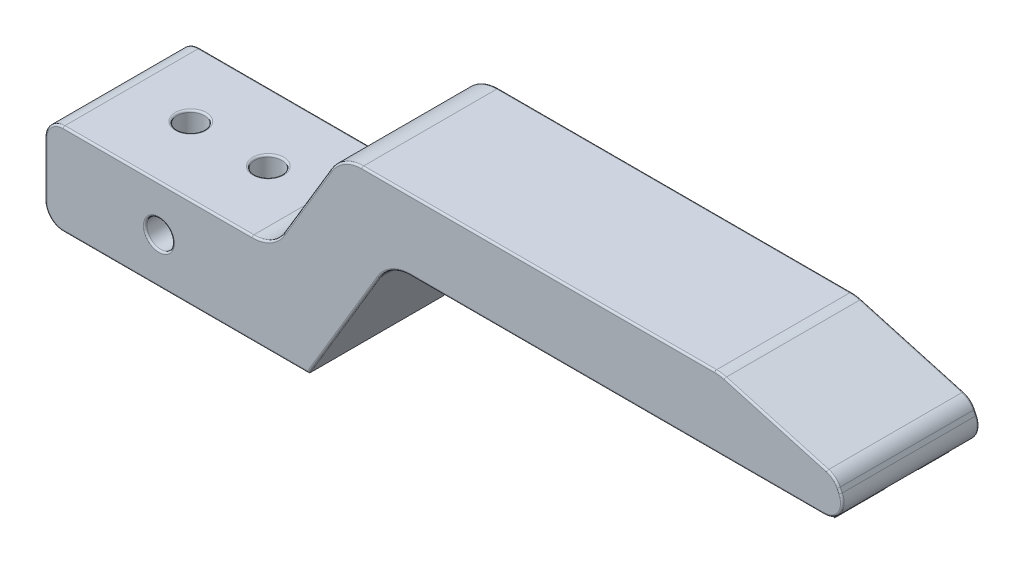
SolidWorks part; units mm, degrees
ref_plane "Plan de face" through (0, 0, 0) normal (0, 0, 1) x (1, 0, 0)
ref_plane "Plan de dessus" through (0, 0, 0) normal (0, 1, 0) x (1, 0, 0)
ref_plane "Plan de droite" through (0, 0, 0) normal (1, 0, 0) x (0, 0, -1)
sketch "Esquisse1" plane through (0, 0, 0) normal (0, 0, 1) x (1, 0, 0)
  line L0 (-20.9618, 39.858) -> (14.6887, 39.858)
  line L1 (14.6887, 39.858) -> (29.918, 39.858)
  line L2 (29.918, 39.858) -> (27.8943, 43.9947)
  line L3 (27.8943, 43.9947) -> (15.2797, 47.558)
  line L4 (15.2797, 47.558) -> (-26.2627, 47.558)
  line L5 (-20.9618, 39.858) -> (-29.8438, 24.9927)
  line L6 (-29.8438, 24.9927) -> (-58.7705, 24.9927)
  line L7 (-58.7705, 24.9927) -> (-58.7705, 34.9927)
  line L8 (-58.7705, 34.9927) -> (-33.7705, 34.9927)
  line L9 (-33.7705, 34.9927) -> (-26.2627, 47.558)
  line L10 (-20.9618, 39.858) -> (-20.9618, 34.2142) construction
  line L11 (-20.9618, 39.858) -> (-62.876, 39.858) construction
  circle A2 centre (-46.2705, 29.9927) radius 1.5
  point P0 (27.8943, 43.9947)
  dimension "D1" = 10
  dimension "D3" = 25
  dimension "D6" = 3
  dimension "D2" = 8.5
  dimension "D4" = 12.5
  dimension "D5" = 5
  dimension "D7" = 7.7
extrude "Boss.-Extru.1" add sketch "Esquisse1" along normal blind 15
fillet "Congé1" radius 2 2 edges at (29.918, 39.858, 7.5) (27.8943, 43.9947, 7.5)
fillet "Congé3" radius 4 1 edges at (-20.9618, 39.858, 7.5)
fillet "Congé5" radius 4 3 edges at (-33.7705, 34.9927, 7.5) (15.2797, 47.558, 7.5) (-26.2627, 47.558, 7.5)
fillet "Congé6" radius 2 2 edges at (-58.7705, 24.9927, 7.5) (-58.7705, 34.9927, 7.5)
sketch "Esquisse2" plane through (0, 24.9927, 0) normal (0, -1, 0) x (1, 0, 0)
  line L1 (-56.7705, 0) -> (-56.7705, 15) construction
  line L2 (-36.0401, 15) -> (-56.7705, 15) construction
  circle A0 centre (-50.2705, 7.5) radius 1.5
  circle A1 centre (-41.7705, 7.5) radius 1.5
  dimension "D2" = 3
  dimension "D4" = 3
  dimension "D1" = 6.5
  dimension "D3" = 7.5
  dimension "D5" = 8.5
extrude "Enlèv. mat.-Extru.2" cut sketch "Esquisse2" against normal through all contours A0 | A1
fillet "Congé8" radius 0.2 4 edges at (-48.7705, 24.9927, 7.5) (-40.2705, 24.9927, 7.5) (-40.2705, 34.9927, 7.5) (-48.7705, 34.9927, 7.5)
sketch "Esquisse3" plane through (0, 39.858, 0) normal (0, -1, 0) x (1, 0, 0)
  line L0 (-17.5068, 13.8) -> (9.5266, 13.8) construction
  line L1 (-18.6922, 15) -> (26.7131, 15) construction
  line L2 (-16.8251, 1.2) -> (4.0259, 1.2) construction
  line L3 (-18.6922, 0) -> (26.7131, 0) construction
  line L4 (-17.4922, 13.0521) -> (-17.4922, 1.8862) construction
  line L5 (-18.6922, 15) -> (-18.6922, 0) construction
  line L6 (26.6973, 11.2262) -> (26.6973, 2.606) construction
  line L7 (-4.5158, 13.8) -> (-10.1726, 13.8)
  line L8 (-0.9802, 13.8) -> (4.6766, 13.8)
  line L13 (8.2122, 13.8) -> (13.869, 13.8)
  line L14 (13.869, 13.8) -> (1.269, 1.2)
  line L17 (17.4045, 13.8) -> (23.0614, 13.8)
  line L18 (23.0614, 13.8) -> (10.4614, 1.2)
  line L19 (10.4614, 1.2) -> (4.8045, 1.2)
  line L20 (4.8045, 1.2) -> (17.4045, 13.8)
  line L21 (26.5969, 13.8) -> (13.9969, 1.2)
  line L22 (13.9969, 1.2) -> (19.6538, 1.2)
  line L25 (26.6973, 4.708) -> (23.1893, 1.2)
  line L29 (19.6538, 1.2) -> (26.6973, 8.2435)
  line L30 (26.6973, 8.2435) -> (26.6973, 13.8)
  line L31 (26.6973, 13.8) -> (26.5969, 13.8)
  line L32 (8.2122, 13.8) -> (-4.3878, 1.2)
  line L33 (-4.3878, 1.2) -> (1.269, 1.2)
  line L34 (4.6766, 13.8) -> (-7.9234, 1.2)
  line L35 (-0.9802, 13.8) -> (-13.5802, 1.2)
  line L36 (-13.5802, 1.2) -> (-7.9234, 1.2)
  line L37 (-4.5158, 13.8) -> (-17.1158, 1.2)
  line L38 (-10.1726, 13.8) -> (-17.4922, 6.4805)
  line L39 (-17.4922, 6.4805) -> (-17.4922, 1.2)
  line L40 (-17.4922, 1.2) -> (-17.1158, 1.2)
  line L41 (-13.7082, 13.8) -> (-17.4922, 10.016)
  line L42 (-17.4922, 10.016) -> (-17.4922, 13.8)
  line L43 (-17.4922, 13.8) -> (-13.7082, 13.8)
  line L44 (23.1893, 1.2) -> (26.6973, 1.2)
  line L45 (26.6973, 1.2) -> (26.6973, 4.708)
  dimension "D1" = 1.2
  dimension "D2" = 1.2
  dimension "D3" = 1.2
  dimension "D4" = 2.5
  dimension "D5" = 4
  dimension "D6" = 2.5
  dimension "D7" = 4
  dimension "D8" = 4
  dimension "D9" = 4
  dimension "D10" = 2.5
  dimension "D12" = 2.5
  dimension "D13" = 2.5
  dimension "D14" = 2.5
extrude "Boss.-Extru.2" add sketch "Esquisse3" along normal blind 1 contours L17 L18 L19 L20 | L13 L14 L33 L32 | L8 L34 L36 L35 | L31 L21 L22 L29 L30 | L43 L41 L42 | L40 L37 L7 L38 L39 | L45 L25 L44
fillet "Congé10" radius 0.2 2 edges at (-44.7705, 29.9927, 0) (-44.7705, 29.9927, 15)
fillet "Congé11" radius 0.2 34 edges at (-58.1847, 34.4069, 15) (-46.4053, 34.9927, 15) (-34.0661, 35.5137, 15) (-30.0166, 41.2754, 15) (-25.9671, 47.037, 15) (-4.6338, 47.558, 15) (15.2744, 47.5202, 15) (21.4236, 45.8225, 15) (27.7722, 43.8483, 15) (28.3984, 42.9644, 15) (28.4098, 40.7992, 15) (4.0105, 39.858, 15) (-20.6662, 39.337, 15) (-25.9849, 31.4512, 15) (-43.3072, 24.9927, 15) (-58.1847, 25.5785, 15) (-58.7705, 29.9927, 15) (-25.9849, 31.4512, 0) (-20.6662, 39.337, 0) (4.0105, 39.858, 0) (28.4098, 40.7992, 0) (28.3984, 42.9644, 0) (27.7722, 43.8483, 0) (21.4236, 45.8225, 0) (15.2744, 47.5202, 0) (-4.6338, 47.558, 0) (-25.9671, 47.037, 0) (-30.0166, 41.2754, 0) (-34.0661, 35.5137, 0) (-46.4053, 34.9927, 0) (-58.1847, 34.4069, 0) (-58.7705, 29.9927, 0) (-58.1847, 25.5785, 0) (-43.3072, 24.9927, 0)
ref_plane "Plan1" through (26.7131, 40.058, 15) normal (1, 0, 0) x (0, 0, -1)
fillet "Congé12" radius 0.2 27 edges at (11.0406, 38.858, 13.8) (7.569, 38.858, 7.5) (1.8482, 38.858, 13.8) (-1.6234, 38.858, 7.5) (20.233, 38.858, 13.8) (16.7614, 38.858, 7.5) (7.633, 38.858, 1.2) (11.1045, 38.858, 7.5) (23.1756, 38.858, 4.7218) (16.8254, 38.858, 1.2) (20.2969, 38.858, 7.5) (26.6973, 38.858, 11.0218) (-1.5594, 38.858, 1.2) (1.9122, 38.858, 7.5) (-10.7518, 38.858, 1.2) (-7.2802, 38.858, 7.5) (24.9433, 38.858, 2.954) (26.6973, 38.858, 2.954) (24.9433, 38.858, 1.2) (-15.6002, 38.858, 13.8) (-15.6002, 38.858, 11.908) (-17.4922, 38.858, 11.908) (-13.8324, 38.858, 10.1402) (-7.3442, 38.858, 13.8) (-10.8158, 38.858, 7.5) (-17.304, 38.858, 1.2) (-17.4922, 38.858, 3.8402)
equation "\"A\"=2"
